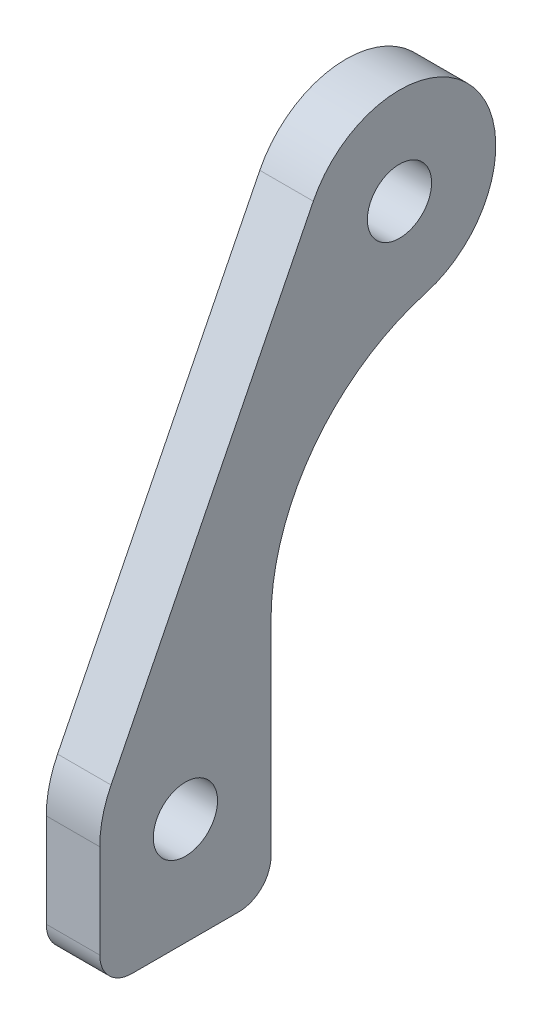
SolidWorks part; units mm, degrees
material "Stal węglowa"
ref_plane "Front" through (0, 0, 0) normal (0, 0, 1) x (1, 0, 0)
ref_plane "Top" through (0, 0, 0) normal (0, 1, 0) x (1, 0, 0)
ref_plane "Right" through (0, 0, 0) normal (1, 0, 0) x (0, 0, -1)
sketch "Szkic1" plane through (0, 0, 0) normal (1, 0, 0) x (0, 0, -1)
  line L228 (-8, -7) -> (-8, 1.7639)
  line L229 (11.9502, 44.0249) -> (-6.9443, 6.2361)
  line L230 (-5, -10) -> (5, -10)
  line L231 (8, 12.1253) -> (8, -7)
  arc A129 (22.4828, 31.3492) -> (11.9502, 44.0249) centre (20, 40) ccw
  circle A130 centre (20, 40) radius 3
  arc A131 (-6.9443, 6.2361) -> (-8, 1.7639) centre (2, 1.7639) ccw
  arc A132 (-8, -7) -> (-5, -10) centre (-5, -7) ccw
  arc A133 (22.4828, 31.3492) -> (8, 12.1253) centre (28, 12.1253) ccw
  arc A134 (5, -10) -> (8, -7) centre (5, -7) ccw
  circle A135 centre (0, 0) radius 3
extrude "Dodanie-wyciągnięcie1" add sketch "Szkic1" along normal blind 5
